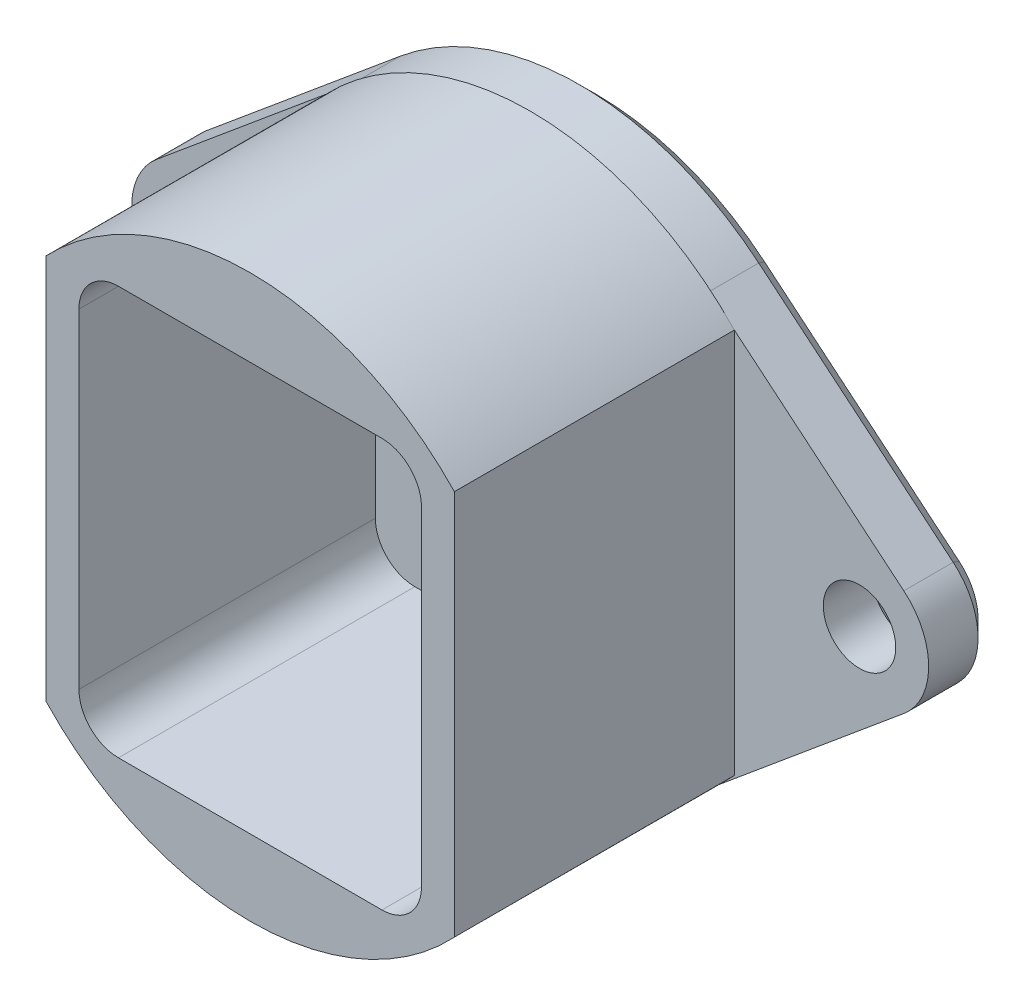
SolidWorks part; units mm, degrees
material "ABS"
ref_plane "Front" through (0, 0, 0) normal (0, 0, 1) x (1, 0, 0)
ref_plane "Top" through (0, 0, 0) normal (0, 1, 0) x (1, 0, 0)
ref_plane "Right" through (0, 0, 0) normal (1, 0, 0) x (0, 0, -1)
sketch "Эскиз2" plane through (0, 0, 0) normal (0, 0, 1) x (1, 0, 0)
  line L0 (5.44, 6.5312) -> (11.344, 1.6136)
  line L1 (11.344, -1.6136) -> (5.44, -6.5312)
  line L2 (-10, 0) -> (10, 0) construction
  line L3 (-5.44, -6.5312) -> (-11.344, -1.6136)
  line L4 (-5.44, 6.5312) -> (-11.344, 1.6136)
  line L5 (0, -8.5) -> (0, 8.5) construction
  arc A1 (11.344, 1.6136) -> (11.344, -1.6136) centre (10, 0) cw
  circle A2 centre (10, 0) radius 1.1
  arc A3 (5.44, -6.5312) -> (-5.44, -6.5312) centre (0, 0) cw
  circle A4 centre (-10, 0) radius 1.1
  arc A5 (-11.344, -1.6136) -> (-11.344, 1.6136) centre (-10, 0) cw
  arc A6 (5.44, 6.5312) -> (-5.44, 6.5312) centre (0, 0) ccw
  circle A7 centre (0, 4.5) radius 1
  circle A9 centre (0, -4.5) radius 1
  circle A10 centre (0, 0) radius 1.7
  point P12 (0, 0)
  dimension "D1" = 2.2
  dimension "D2" = 2.1
  dimension "D4" = 17
  dimension "D5" = 2
  dimension "D7" = 3.4
  dimension "D3" = 20
  dimension "D6" = 9
extrude "Основание" add sketch "Эскиз2" along normal blind 2
sketch "Эскиз3" plane through (0, 0, 2) normal (0, 0, 1) x (1, 0, 0)
  line L0 (11.344, 1.6136) -> (5.44, 6.5312) construction
  line L1 (6.2, 5.8982) -> (6.2, -5.8146)
  line L2 (4, 6.2) -> (-4, 6.2)
  line L3 (5.2, 5) -> (5.2, -5)
  line L4 (4, -6.2) -> (-4, -6.2)
  line L5 (-5.2, 5) -> (-5.2, -5)
  line L6 (5.2, 6.2) -> (-5.2, -6.2) construction
  line L7 (5.2, -6.2) -> (-5.2, 6.2) construction
  line L8 (-6.2, -5.8146) -> (-6.2, 5.8982)
  arc A1 (-4, -6.2) -> (-5.2, -5) centre (-4, -5) cw
  arc A2 (6.2, -5.8146) -> (-6.2, -5.8146) centre (0, 0) cw
  arc A3 (-5.44, -6.5312) -> (5.44, -6.5312) centre (0, 0) ccw construction
  arc A4 (6.2, 5.8982) -> (-6.2, 5.8982) centre (0, 0) ccw
  arc A6 (4, -6.2) -> (5.2, -5) centre (4, -5) ccw
  arc A7 (5.2, 5) -> (4, 6.2) centre (4, 5) ccw
  arc A8 (-4, 6.2) -> (-5.2, 5) centre (-4, 5) ccw
  circle A10 centre (0, 0) radius 7.6031 construction
  dimension "D1" = 12.4
  dimension "D3" = 1
  dimension "D4" = 1.2
  dimension "D5" = 0.9542
  dimension "D2" = 10.4
extrude "Стенки" add sketch "Эскиз3" along normal offset from surface (8.5 mm away) 10.5 up to face at (0, 0, 0)
sketch "Эскиз4" plane through (0, 0, 2) normal (0, 0, 1) x (1, 0, 0)
  line L0 (5.2, -5) -> (5.2, 5) construction
  line L1 (-4, -6.2) -> (4, -6.2)
  line L2 (-5.2, -5) -> (-5.2, 5)
  line L3 (-4, 6.2) -> (4, 6.2)
  line L4 (5.2, -5) -> (5.2, 5)
  line L5 (-5.2, -6.2) -> (5.2, 6.2) construction
  line L6 (-5.2, 6.2) -> (5.2, -6.2) construction
  arc A0 (4, -6.2) -> (5.2, -5) centre (4, -5) ccw
  arc A1 (4, 6.2) -> (5.2, 5) centre (4, 5) cw
  arc A2 (-4, 6.2) -> (-5.2, 5) centre (-4, 5) ccw
  arc A3 (-5.2, -5) -> (-4, -6.2) centre (-4, -5) ccw
  arc A4 (4, -6.2) -> (5.2, -5) centre (4, -5) ccw construction
  point P0 (0, 0)
extrude "Вырез дополнительный" cut sketch "Эскиз4" against normal blind 0.5
sketch "Эскиз5" plane through (0, 0, 1.5) normal (0, 0, 1) x (1, 0, 0)
  circle A0 centre (0, 0) radius 2.25
  dimension "D1" = 4.5
extrude "Вырез под ободок вала" cut sketch "Эскиз5" against normal blind 0.9
chamfer "Фаска под винты М1.6" distance 0.8 angle 45 2 edges at (-1, -4.5, 0) (1, 4.5, 0)
chamfer "Фаска1" distance 0.5 angle 45 11 edges at (-8.9, 0, 0) (1.7, 0, 0) (11.1, 0, 0) (-8.392, 4.0724, 0) (-12.1, 0, 0) (-8.392, -4.0724, 0) (8.392, -4.0724, 0) (12.1, 0, 0) (8.392, 4.0724, 0) (0, -8.5, 0) (0, 8.5, 0)
